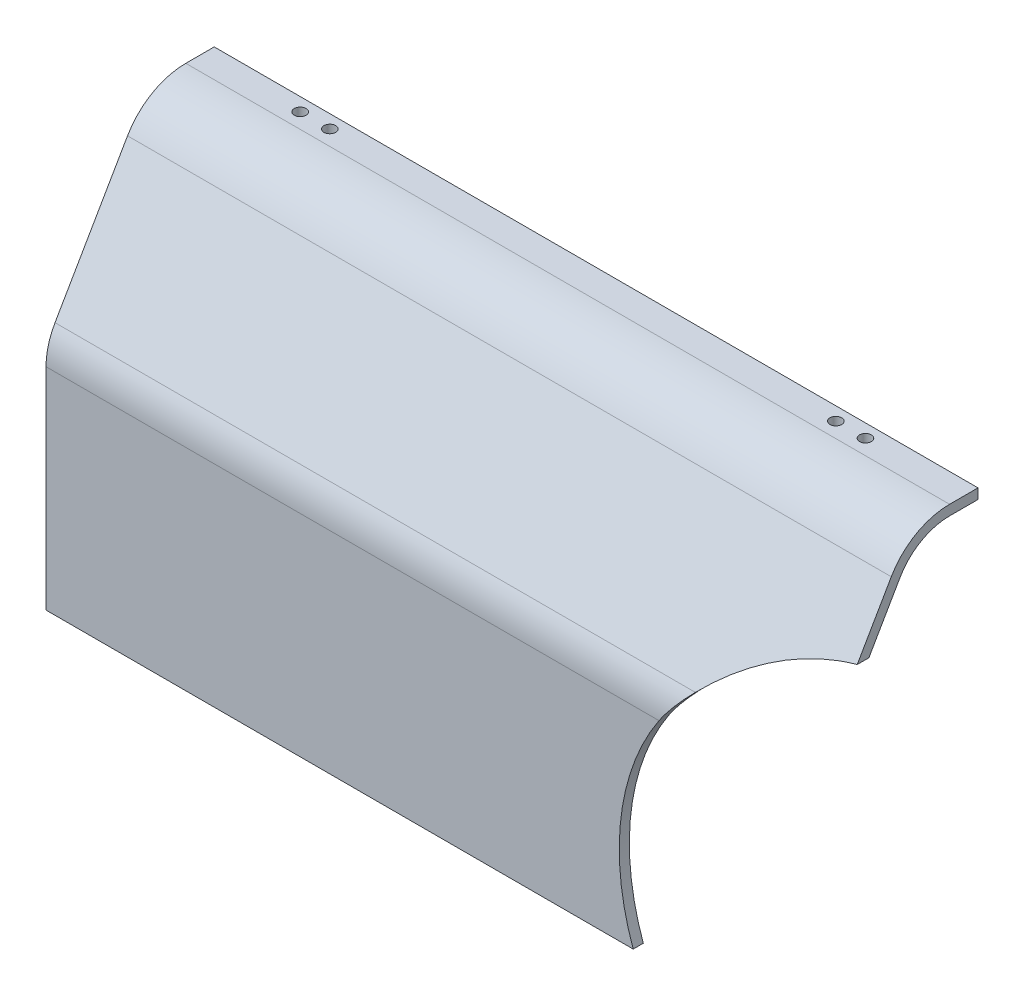
SolidWorks part; units mm, degrees
ref_plane "Alzado" through (0, 0, 0) normal (0, 0, 1) x (1, 0, 0)
ref_plane "Planta" through (0, 0, 0) normal (0, 1, 0) x (1, 0, 0)
ref_plane "Vista lateral" through (0, 0, 0) normal (1, 0, 0) x (0, 0, -1)
sketch "Croquis1" plane through (0, 0, 0) normal (1, 0, 0) x (0, 0, -1)
  line L0 (0, 0) -> (0, 67.1962)
  line L1 (0, 67.1962) -> (28.7321, 116.9615)
  line L2 (28.7321, 116.9615) -> (47, 116.9615)
  line L3 (47, 116.9615) -> (47, 119.9615)
  line L4 (47, 119.9615) -> (27, 119.9615)
  line L5 (27, 119.9615) -> (-3, 68)
  line L6 (-3, 68) -> (-3, 0)
  line L7 (-3, 0) -> (0, 0)
  line L8 (0, 67.1962) -> (29.2398, 67.1962) construction
  dimension "D1" = 3
  dimension "D2" = 3
  dimension "D3" = 3
  dimension "D4" = 68
  dimension "D5" = 60
  dimension "D6" = 20
  dimension "D7" = 60
extrude "Saliente-Extruir1" add sketch "Croquis1" along normal mid plane 227
fillet "Redondeo1" radius 20 1 edges at (0, 68, 3)
fillet "Redondeo2" radius 20 1 edges at (0, 119.9615, -27)
fillet "Redondeo3" radius 17 1 edges at (0, 116.9615, -28.7321)
fillet "Redondeo4" radius 17 1 edges at (0, 67.1962, 0)
sketch "Croquis2" plane through (0, 0, 3) normal (0, 0, 1) x (1, 0, 0)
  circle A0 centre (126.88, 23.7215) radius 70
  dimension "D1" = 140
  dimension "D2" = 13.38
  dimension "D3" = 86.24
extrude "Cortar-Extruir1" cut sketch "Croquis2" against normal through all
sketch "Croquis3" plane through (0, 119.9615, 0) normal (0, 1, 0) x (1, 0, 0)
  circle A0 centre (-84, 43.047) radius 1.75
  circle A1 centre (-75.2, 43.047) radius 1.75
  circle A2 centre (75.2, 43.047) radius 1.75
  circle A3 centre (84, 43.047) radius 1.75
extrude "Cortar-Extruir2" cut sketch "Croquis3" against normal blind 20
